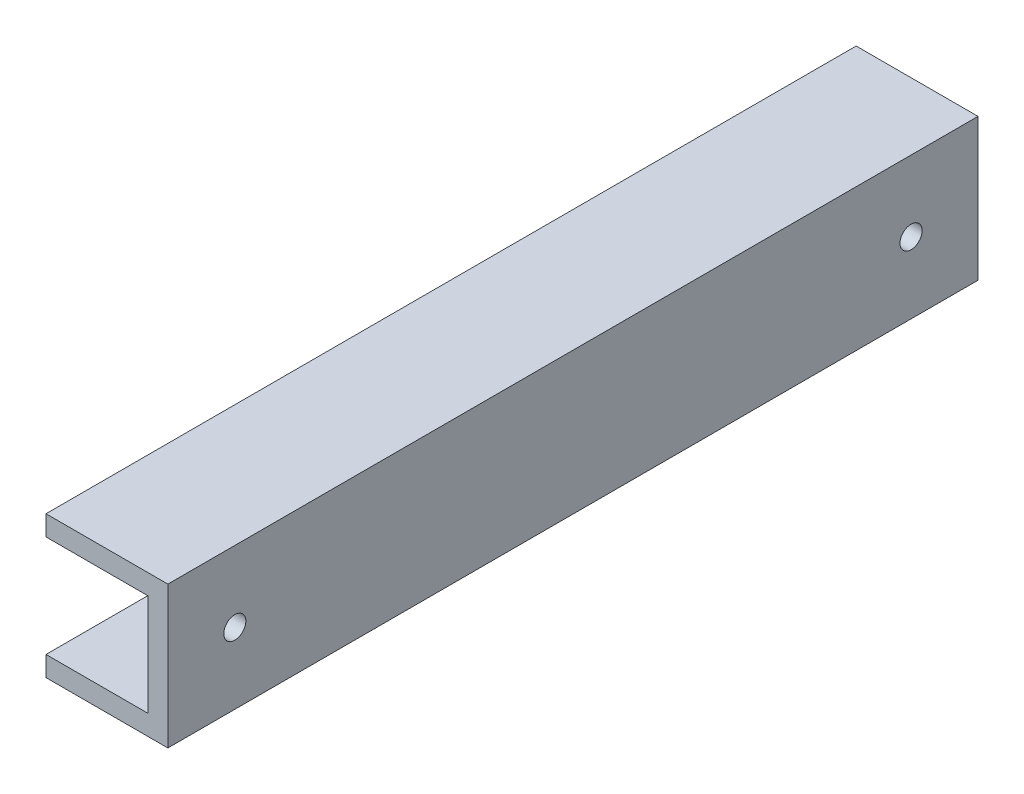
SolidWorks part; units mm, degrees
ref_plane "前视基准面" through (0, 0, 0) normal (0, 0, 1) x (1, 0, 0)
ref_plane "上视基准面" through (0, 0, 0) normal (0, 1, 0) x (1, 0, 0)
ref_plane "右视基准面" through (0, 0, 0) normal (1, 0, 0) x (0, 0, -1)
sketch "草图1" plane through (0, 0, 0) normal (0, 0, 1) x (1, 0, 0)
  line L1 (0, 0) -> (15.2, 0)
  line L2 (0, 0) -> (0, 15.2)
  line L3 (0, 15.2) -> (15.2, 15.2)
  line L4 (15.2, 0) -> (15.2, 15.2)
  dimension "D1" = 15.2
  dimension "D2" = 15.2
extrude "拉伸-薄壁1" add sketch "草图1" along normal blind 121 thin thin type one direction wall 3
sketch "草图2" plane through (-3, 0, 0) normal (-1, 0, 0) x (0, 0, 1)
  line L0 (0, 18.2) -> (0, -3) construction
  line L1 (121, 18.2) -> (121, -3) construction
  line L2 (121, -3) -> (0, -3) construction
  circle A0 centre (10, 7.6) radius 1.65
  circle A1 centre (111, 7.6) radius 1.65
  dimension "D1" = 3.3
  dimension "D2" = 3.3
  dimension "D3" = 10
  dimension "D4" = 10
  dimension "D5" = 10.6
extrude "切除-拉伸1" cut sketch "草图2" against normal blind 30
sketch "草图3" plane through (-3, 0, 0) normal (-1, 0, 0) x (0, 0, 1)
  line L1 (-5.2954, 23.3125) -> (308.7578, 23.3125)
  line L2 (-5.2954, 23.3125) -> (-5.2954, -22.907)
  line L3 (-5.2954, -22.907) -> (308.7578, -22.907)
  line L4 (308.7578, 23.3125) -> (308.7578, -22.907)
extrude "切除-拉伸2" cut sketch "草图3" against normal blind 3
sketch "草图4" plane through (15.2, 0, 0) normal (-1, 0, 0) x (0, 0, 1)
  line L0 (121, 15.2) -> (0, 15.2) construction
  line L1 (25, 15.2) -> (30, 15.2)
  line L2 (25, 15.2) -> (25, 0)
  line L3 (25, 0) -> (30, 0)
  line L4 (30, 15.2) -> (30, 0)
  line L5 (121, 0) -> (0, 0) construction
  line L6 (121, 15.2) -> (0, 15.2) construction
  line L7 (91, 15.2) -> (96, 15.2)
  line L8 (91, 15.2) -> (91, 0)
  line L9 (91, 0) -> (96, 0)
  line L10 (96, 15.2) -> (96, 0)
  line L11 (121, 0) -> (0, 0) construction
  line L12 (121, 0) -> (121, 15.2) construction
  line L13 (0, 0) -> (0, 15.2) construction
  dimension "D1" = 25
  dimension "D2" = 25
  dimension "D3" = 5
  dimension "D4" = 5
extrude "凸台-拉伸1" add sketch "草图4" along normal blind 10
sketch "草图5" plane through (15.2, 0, 0) normal (-1, 0, 0) x (0, 0, 1)
  line L0 (30, 0) -> (30, 15.2) construction
  line L1 (30, 10.1) -> (91, 10.1)
  line L2 (30, 10.1) -> (30, 5.1)
  line L3 (30, 5.1) -> (91, 5.1)
  line L4 (91, 10.1) -> (91, 5.1)
  line L5 (91, 15.2) -> (91, 0) construction
  line L6 (91, 0) -> (30, 0) construction
  dimension "D1" = 5
  dimension "D2" = 5.1
extrude "凸台-拉伸2" add sketch "草图5" along normal blind 10
sketch "草图6" plane through (15.2, 0, 0) normal (-1, 0, 0) x (0, 0, 1)
  line L1 (25, 15.2) -> (96, 15.2)
  line L2 (25, 15.2) -> (25, 0)
  line L3 (25, 0) -> (96, 0)
  line L4 (96, 15.2) -> (96, 0)
extrude "凸台-拉伸3" add sketch "草图6" along normal blind 10
sketch "草图7" plane through (5.2, 0, 0) normal (-1, 0, 0) x (0, 0, 1)
  line L0 (25, 15.2) -> (25, 0) construction
  line L1 (25, 11.2) -> (96, 11.2)
  line L2 (25, 11.2) -> (25, 6.2)
  line L3 (25, 6.2) -> (96, 6.2)
  line L4 (96, 11.2) -> (96, 6.2)
  line L5 (96, 0) -> (96, 15.2) construction
  line L6 (121, 15.2) -> (0, 15.2) construction
  dimension "D1" = 5
  dimension "D2" = 4
extrude "凸台-拉伸4" [suppressed] add sketch "草图7" along normal blind 3
sketch "草图8" plane through (5.2, 0, 0) normal (-1, 0, 0) x (0, 0, 1)
  line L0 (25, 15.2) -> (25, 0) construction
  line L1 (25, 10.1) -> (96, 10.1)
  line L2 (25, 10.1) -> (25, 5.1)
  line L3 (25, 5.1) -> (96, 5.1)
  line L4 (96, 10.1) -> (96, 5.1)
  line L5 (96, 0) -> (96, 15.2) construction
  line L6 (121, 15.2) -> (0, 15.2) construction
  dimension "D1" = 5
  dimension "D2" = 5.1
extrude "切除-拉伸3" cut sketch "草图8" against normal blind 3
chamfer "倒角1" distance 3 angle 45 2 edges at (8.2, 7.6, 96) (8.2, 7.6, 25)
chamfer "倒角2" distance 4 angle 45 2 edges at (15.2, 7.6, 96) (15.2, 7.6, 25)
